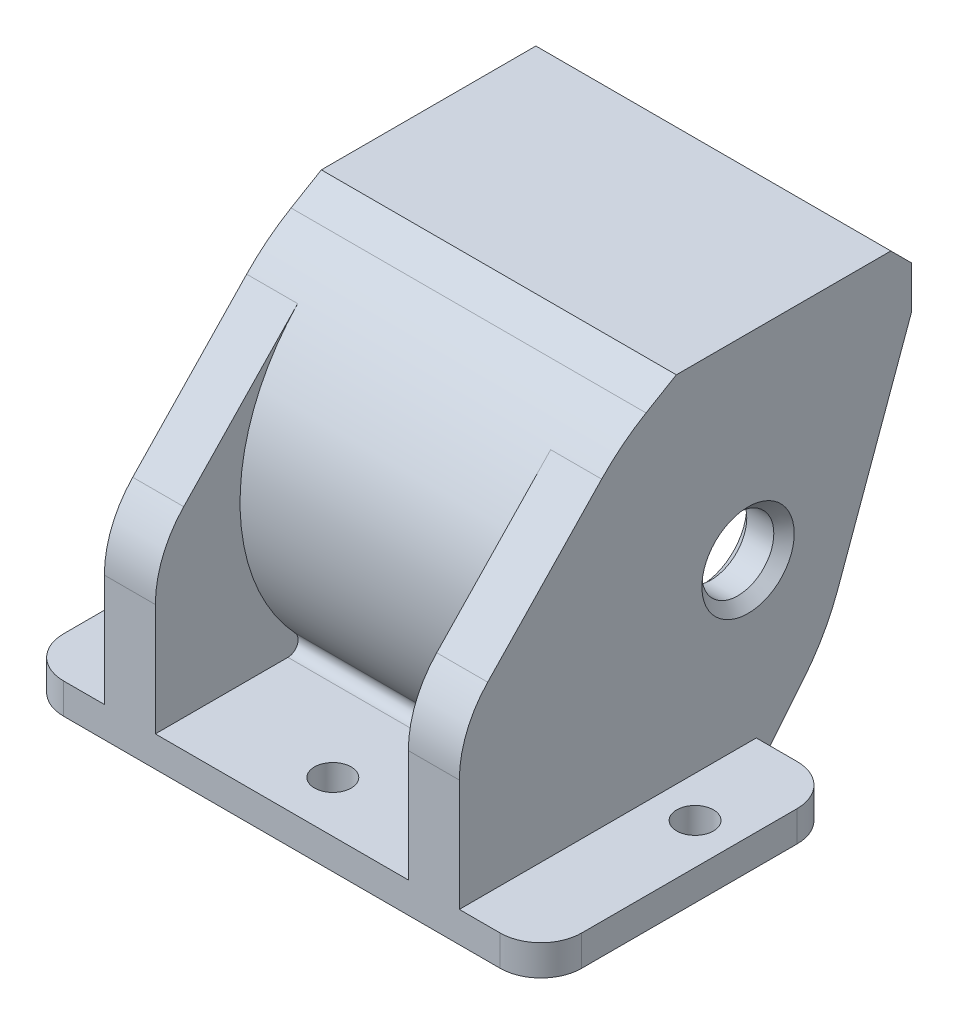
SolidWorks part; units mm, degrees
ref_plane "Front Plane" through (0, 0, 0) normal (0, 0, 1) x (1, 0, 0)
ref_plane "Top Plane" through (0, 0, 0) normal (0, 1, 0) x (1, 0, 0)
ref_plane "Right Plane" through (0, 0, 0) normal (1, 0, 0) x (0, 0, -1)
sketch "Sketch1" plane through (0, 0, 0) normal (1, 0, 0) x (0, 0, -1)
  line L0 (0, 17.5) -> (0, -17.5) construction
  line L1 (0, 17.5) -> (-10, 17.5)
  line L2 (10, 17.5) -> (10, -17.5) construction
  line L3 (0, -17.5) -> (-10, -17.5)
  line L4 (-10, 17.5) -> (-10, -17.5) construction
  line L5 (0, 0) -> (10, 0) construction
  line L6 (0, 0) -> (-10, 0) construction
  line L7 (0, 0) -> (-10, 0) construction
  line L8 (-10, 0) -> (-20, 0) construction
  arc A0 (0, -17.5) -> (0, 17.5) centre (-10.3125, 0) ccw
  arc A1 (-10, 17.5) -> (-10, -17.5) centre (0.3125, 0) ccw
  dimension "D3" = 20
  dimension "D1" = 35
extrude "Boss-Extrude1" add sketch "Sketch1" against normal mid plane 34.8
sketch "Sketch2" plane through (0, 0, 0) normal (1, 0, 0) x (0, 0, -1)
  line L0 (0, 17.5) -> (-10, 17.5) construction
  line L1 (-10, -17.5) -> (0, -17.5) construction
  line L2 (-16, 0) -> (-20, 0) construction
  line L4 (-10, -17.5) -> (0, -17.5)
  line L5 (0, 17.5) -> (-10, 17.5)
  line L6 (-6, -17.5) -> (0, -17.5)
  line L7 (0, 17.5) -> (-6, 17.5)
  arc A0 (-6, 17.5) -> (-6, -17.5) centre (4.3125, 0) ccw
  arc A1 (-10, 17.5) -> (-10, -17.5) centre (0.3125, 0) ccw construction
  arc A4 (-10, 17.5) -> (-10, -17.5) centre (0.3125, 0) ccw
  arc A5 (0, -17.5) -> (0, 17.5) centre (-10.3125, 0) ccw
  arc A7 (0, -17.5) -> (0, 17.5) centre (-10.3125, 0) ccw
  dimension "D1" = 0
  dimension "D2" = 4
extrude "Cut-Extrude1" cut sketch "Sketch2" along normal mid plane 25.5
sketch "Sketch3" plane through (0, 0, 0) normal (1, 0, 0) x (0, 0, -1)
  line L0 (-9.5, -17.5) -> (-9.5, -24)
  line L1 (-10, -17.5) -> (0, -17.5) construction
  line L2 (-0.5, -24) -> (-0.5, -17.5)
  line L3 (-0.5, -17.5) -> (-9.5, -17.5)
  line L4 (-5, -28.5) -> (-5, -17.5) construction
  arc A0 (-9.5, -24) -> (-0.5, -24) centre (-5, -24) ccw
  dimension "D1" = 9
  dimension "D2" = 6.5
extrude "Boss-Extrude2" add sketch "Sketch3" along normal mid plane 10
sketch "Sketch4" plane through (17.4, 0, 0) normal (1, 0, 0) x (0, 0, -1)
  line L0 (-13.4374, -9.8761) -> (0.9816, -18.201)
  line L1 (0.8089, -18.5) -> (-8.303, -18.5)
  line L4 (-13.4374, -9.8761) -> (-17.4374, -9.8761)
  line L5 (0.8089, -18.5) -> (0.9816, -18.201)
  line L8 (0, 0) -> (14.9634, 0.0217) construction
  line L9 (14.9634, 0.0217) -> (14.9855, -15.25) construction
  line L10 (69.9999, 0.1014) -> (0, 0) construction
  line L12 (-10, -17.5) -> (-8.303, -18.5)
  line L13 (0.9816, -18.201) -> (8.6174, -4.9753) construction
  line L14 (0, 0) -> (8.6174, -4.9753) construction
  line L15 (0, 0) -> (-8.348, 0) construction
  line L16 (-10, -17.5) -> (0, -17.5) construction
  arc A0 (-10, 17.5) -> (-10, -17.5) centre (0.3125, 0) ccw construction
  arc A2 (-6, 17.5) -> (-6, -17.5) centre (4.3125, 0) ccw construction
  arc A3 (-6, 17.5) -> (-6, -17.5) centre (4.3125, 0) ccw construction
  arc A4 (-17.4374, -9.8761) -> (-10, -17.5) centre (0.3125, 0) ccw
  dimension "D1" = 30
  dimension "D2" = 0.299
  dimension "D3" = 1
extrude "Boss-Extrude3" add sketch "Sketch4" against normal up to surface (34.8 mm away) up to face at (-17.4, 0, 5)
sketch "Sketch5" plane through (17.4, 0, 0) normal (1, 0, 0) x (0, 0, -1)
  line L4 (-8.303, -18.5) -> (0.8089, -18.5) construction
  line L5 (5.426, -12.8412) -> (0.8089, -18.5)
  line L6 (0.8089, -18.5) -> (0.9816, -18.201) construction
  line L7 (0.8089, -18.5) -> (-1.1911, -18.5)
  line L8 (-1.1911, -18.5) -> (-1.1911, -17.5)
  line L9 (-1.1911, -17.5) -> (5.426, -12.8412)
  arc A3 (0, -17.5) -> (0, 17.5) centre (-10.3125, 0) ccw construction
  dimension "D1" = 1
  dimension "D2" = 2
extrude "Boss-Extrude4" add sketch "Sketch5" against normal up to surface (4.65 mm away) up to face at (12.75, -1.6725, 3.0481)
sketch "Sketch6" plane through (-17.4, 0, 0) normal (-1, 0, 0) x (0, 0, 1)
  line L2 (-5.426, -12.8412) -> (-0.8089, -18.5)
  line L3 (-5.426, -12.8412) -> (-0.8089, -18.5)
  line L4 (-0.8089, -18.5) -> (1.1911, -18.5)
  line L5 (-0.8089, -18.5) -> (1.1911, -18.5)
  line L12 (1.1911, -18.5) -> (1.1911, -17.5)
  line L13 (1.1911, -18.5) -> (1.1911, -17.5)
  line L14 (1.1911, -17.5) -> (-5.426, -12.8412)
  line L15 (1.1911, -17.5) -> (-5.426, -12.8412)
  dimension "D1" = 0
extrude "Boss-Extrude5" add sketch "Sketch6" against normal up to surface (4.65 mm away) up to face at (-12.75, -1.6725, 3.0481)
sketch "Sketch7" plane through (17.4, 0, 0) normal (1, 0, 0) x (0, 0, -1)
  line L0 (-10, 17.5) -> (-7.0303, 19.25)
  line L1 (-7.0303, 19.25) -> (16, 19.25)
  line L2 (16, 19.25) -> (16, 12.9763)
  line L3 (0, 0) -> (2.6687, 15.0147) construction
  line L4 (3.1052, 15.25) -> (-13.1052, 15.25)
  line L6 (0, 0) -> (0, 15.25) construction
  line L7 (68.9198, -12.25) -> (0, 0) construction
  line L8 (86.7312, 0.0732) -> (32.7778, 9.663) construction
  line L9 (0, 17.5) -> (-10, 17.5) construction
  line L10 (3.1052, 15.25) -> (16, 12.9763)
  line L11 (0, 17.5) -> (-10, 17.5) construction
  line L13 (10, 0) -> (10, 11.0966) construction
  line L14 (0, 0) -> (68.9198, 0) construction
  arc A0 (-10, 17.5) -> (-10, -17.5) centre (0.3125, 0) ccw construction
  arc A1 (-10, 17.5) -> (-13.1052, 15.25) centre (0.3125, 0) ccw
  arc A3 (5.426, -12.8412) -> (0, 17.5) centre (-10.3125, 0) ccw construction
  dimension "D1" = 10
  dimension "D2" = 4
  dimension "D3" = 6
extrude "Boss-Extrude6" add sketch "Sketch7" against normal up to surface (34.8 mm away) up to face at (-17.4, -5.1825, 4.1831)
sketch "Sketch8" plane through (17.4, 0, 0) normal (1, 0, 0) x (0, 0, -1)
  line L0 (16, 12.9763) -> (8.7832, -6.9248)
  line L2 (3.1052, 15.25) -> (16, 12.9763)
  arc A0 (5.426, -12.8412) -> (3.1052, 15.25) centre (-10.3125, 0) ccw construction
  arc A1 (8.7832, -6.9248) -> (3.1052, 15.25) centre (-10.3125, 0) ccw
extrude "Boss-Extrude7" add sketch "Sketch8" against normal up to surface (4.65 mm away) up to face at (12.75, -4.6143, 1.8315)
sketch "Sketch9" plane through (-17.4, 0, 0) normal (-1, 0, 0) x (0, 0, 1)
  line L2 (-16, 12.9763) -> (-8.7832, -6.9248)
  line L3 (-3.1052, 15.25) -> (-16, 12.9763)
  line L4 (-16, 12.9763) -> (-8.7832, -6.9248)
  line L5 (-3.1052, 15.25) -> (-16, 12.9763)
  arc A1 (-3.1052, 15.25) -> (-8.7832, -6.9248) centre (10.3125, 0) ccw
  arc A2 (-3.1052, 15.25) -> (-8.7832, -6.9248) centre (10.3125, 0) ccw
  dimension "D1" = 0
extrude "Boss-Extrude8" add sketch "Sketch9" against normal up to surface (4.65 mm away) up to face at (-12.75, -4.6143, 1.8315)
chamfer "Chamfer2" distance 2 angle 45 1 edges at (0, 19.25, -16)
sketch "Sketch10" plane through (17.4, 0, 0) normal (1, 0, 0) x (0, 0, -1)
  circle A0 centre (0, 0) radius 3.175 construction
  circle A1 centre (0, 0) radius 3.525
  dimension "D1" = 6.35
  dimension "D2" = 0.35
extrude "Cut-Extrude2" cut sketch "Sketch10" against normal through all
sketch "Sketch11" plane through (0, 0, 0) normal (1, 0, 0) x (0, 0, -1)
  line L3 (-9.5, -17.5) -> (-9.5, -24)
  line L4 (-0.5, -24) -> (-0.5, -17.5)
  line L5 (-0.5, -17.5) -> (-9.5, -17.5)
  line L6 (-9.5, -17.5) -> (-9.5, -24)
  line L7 (-0.5, -24) -> (-0.5, -17.5)
  line L8 (-0.5, -17.5) -> (-9.5, -17.5)
  arc A1 (-9.5, -24) -> (-0.5, -24) centre (-5, -24) ccw
  arc A2 (-9.5, -24) -> (-0.5, -24) centre (-5, -24) ccw
  dimension "D1" = 0
extrude "Cut-Extrude3" cut sketch "Sketch11" against normal mid plane 0.762
chamfer "Chamfer3" [suppressed] distance 5 angle 45
sketch "Sketch12" plane through (0, -18.5, 0) normal (0, -1, 0) x (1, 0, 0)
  line L0 (-17.4, -0.8089) -> (-21.4, -0.8089)
  line L2 (21.4, -0.8089) -> (17.4, -0.8089)
  line L4 (-25.4, 22.303) -> (25.4, 22.303) construction
  line L8 (-25.4, 3.1911) -> (-25.4, 22.303)
  line L9 (25.4, 22.303) -> (25.4, 3.1911)
  line L10 (-17.4, 8.303) -> (-25.4, 8.303) construction
  line L11 (0, 22.303) -> (0, 28.303) construction
  line L12 (-17.4, -0.8089) -> (-17.4, 8.303) construction
  line L13 (17.4, 8.303) -> (25.4, 8.303) construction
  line L14 (17.4, 8.303) -> (17.4, -0.8089) construction
  line L15 (-17.4, -0.8089) -> (-17.4, 8.303)
  line L16 (17.4, 8.303) -> (17.4, -0.8089)
  line L17 (17.4, 8.303) -> (-17.4, 8.303)
  line L18 (-25.4, 22.303) -> (-25.4, 24.303)
  line L19 (-21.4, 28.303) -> (21.4, 28.303)
  line L20 (25.4, 24.303) -> (25.4, 22.303)
  arc A0 (-21.4, -0.8089) -> (-25.4, 3.1911) centre (-21.4, 3.1911) cw
  arc A1 (25.4, 3.1911) -> (21.4, -0.8089) centre (21.4, 3.1911) cw
  arc A2 (-25.4, 22.303) -> (25.4, 22.303) centre (0, -28.4603) cw construction
  arc A3 (21.4, 28.303) -> (25.4, 24.303) centre (21.4, 24.303) cw
  arc A4 (-25.4, 24.303) -> (-21.4, 28.303) centre (-21.4, 24.303) cw
  dimension "D2" = 4
  dimension "D5" = 4
  dimension "D1" = 8
  dimension "D3" = 6
  dimension "D4" = 14
extrude "Boss-Extrude9" add sketch "Sketch12" against normal blind 3
sketch "Sketch13" plane through (-17.4, 0, 0) normal (-1, 0, 0) x (0, 0, 1)
  line L0 (20, -15.5) -> (12.8156, -15.5)
  line L1 (20, -15.5) -> (20, 0) construction
  line L3 (12.8156, -15.5) -> (12.8156, -23.5)
  line L4 (12.8156, -23.5) -> (20, -23.5)
  line L5 (20, -23.5) -> (20, -15.5)
  line L6 (24.303, -18.5) -> (3.1911, -18.5) construction
  arc A0 (20, 0) -> (12.8156, -15.5) centre (-0.3125, 0) cw construction
  arc A1 (12.8156, -15.5) -> (10, 17.5) centre (-0.3125, 0) ccw construction
  dimension "D1" = 5
extrude "Boss-Extrude10" add sketch "Sketch13" against normal blind 5
sketch "Sketch22" plane through (-17.4, 0, 0) normal (-1, 0, 0) x (0, 0, 1)
  line L0 (14.3518, 14.0555) -> (25.5224, 2.4011)
  line L1 (28.303, -4.5185) -> (28.303, -15.5)
  line L2 (12.8156, -15.5) -> (28.303, -15.5)
  arc A0 (12.8156, -15.5) -> (10, 17.5) centre (-0.3125, 0) ccw construction
  arc A1 (12.8156, -15.5) -> (14.3518, 14.0555) centre (-0.3125, 0) ccw
  arc A2 (25.5224, 2.4011) -> (28.303, -4.5185) centre (18.303, -4.5185) cw
  point P9 (28.303, -0.5)
  dimension "D2" = 10
  dimension "D1" = 15
extrude "Boss-Extrude13" add sketch "Sketch22" against normal blind 5
mirror "Mirror1" about plane through (0, 0, 0) normal (1, 0, 0) of "Boss-Extrude13", "Boss-Extrude10"
hole_wizard "M3 Clearance Hole1" positions "Sketch14" profile "Sketch15" hole size "M3" standard "ANSI Metric" end condition through all
sketch "Sketch14" plane through (0, -15.5, 0) normal (0, 1, 0) x (1, 0, 0)
  line L3 (0, -23.303) -> (0, -28.303) construction
  line L4 (-21.4, 0.8089) -> (-21.4, -9.1911) construction
  line L6 (21.4, 0.8089) -> (21.4, -9.1911) construction
  line L7 (25.4, -28.303) -> (-25.4, -28.303) construction
  point P10 (0, -23.303)
  point P34 (-21.4, -9.1911)
  point P36 (21.4, -9.1911)
  dimension "D1" = 5
  dimension "D2" = 10
sketch "Sketch15" plane through (0, -15.5, 23.303) normal (1, 0, 0) x (0, 0, 1)
  line L0 (0, 0) -> (0, 13)
  line L1 (0, 13) -> (1.8, 13)
  line L2 (1.8, 13) -> (1.8, 0)
  line L5 (1.8, 0) -> (0, 0)
  line L11 (0, -6.35) -> (0, 107.95) construction
  dimension "Thru Hole Dia." = 3.6
  dimension "Thru Hole Depth" = 13
hole_wizard "M3 Clearance Hole2" positions "Sketch16" profile "Sketch17" hole size "M3" standard "ANSI Metric" end condition through all
sketch "Sketch16" plane through (5, 0, 0) normal (1, 0, 0) x (0, 0, -1)
  point P0 (-5, -24)
sketch "Sketch17" plane through (5, -24, 5) normal (0, 1, 0) x (0, 0, -1)
  line L0 (0, 0) -> (0, 30.4)
  line L1 (0, 30.4) -> (1.8, 30.4)
  line L2 (1.8, 30.4) -> (1.8, 0)
  line L5 (1.8, 0) -> (0, 0)
  line L11 (0, -6.35) -> (0, 107.95) construction
  dimension "Thru Hole Dia." = 3.6
  dimension "Thru Hole Depth" = 30.4
chamfer "Chamfer5" distance 1 angle 45 4 edges at (17.4, 0, -3.525) (-12.75, 0, -3.525) (-17.4, 0, -3.525) (12.75, 0, -3.525)
sketch "Sketch18" plane through (0, 0, 0) normal (1, 0, 0) x (0, 0, -1)
  line L0 (0.9816, -18.201) -> (-13.4374, -9.8761)
  line L1 (-0.2321, -17.5002) -> (-13.4374, -9.8761) construction
  line L2 (-11.421, -18.5) -> (-0.5, -18.5) construction
  line L3 (-3.1911, -18.5) -> (-24.303, -18.5) construction
  line L4 (-0.5, -18.5) -> (1.4995, -18.5)
  line L5 (1.4995, -18.5) -> (-0.2321, -17.5002)
  arc A0 (-0.2321, -17.5002) -> (-0.5, -18.5) centre (-0.5, -17.9642) cw
extrude "Cut-Extrude4" cut sketch "Sketch18" against normal up to surface and the other way up to surface up to face at (-12.75, 0, -4.525) other way up to face at (12.75, 0, -4.525)
chamfer "Chamfer6" distance 1 angle 45 8 edges at (-14.9, -23.5, 20) (-12.4, -23.5, 16.4078) (-14.9, -23.5, 12.8156) (-17.4, -23.5, 16.4078) (14.9, -23.5, 12.8156) (12.4, -23.5, 16.4078) (17.4, -23.5, 16.4078) (14.9, -23.5, 20)
fillet "Fillet1" radius 1 1 edges at (0, -15.5, 12.8156)
